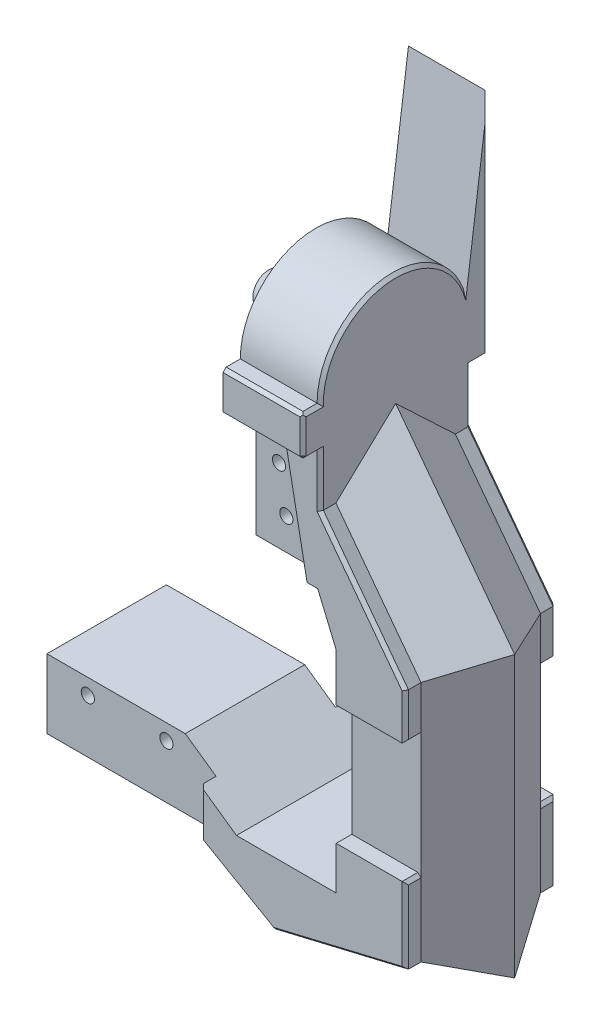
SolidWorks part; units mm, degrees
ref_plane "前视基准面" through (0, 0, 0) normal (0, 0, 1) x (1, 0, 0)
ref_plane "上视基准面" through (0, 0, 0) normal (0, 1, 0) x (1, 0, 0)
ref_plane "右视基准面" through (0, 0, 0) normal (1, 0, 0) x (0, 0, -1)
other "Configuration Table"
sketch "草图1" plane through (0, 0, 0) normal (0, 0, 1) x (1, 0, 0)
  line L0 (0, 0) -> (53.8, 0)
  line L1 (53.8, 0) -> (77, -13.3945)
  line L2 (77, -13.3945) -> (119, -3.4144)
  line L3 (119, -3.4144) -> (119, 73.5856)
  line L4 (119, 73.5856) -> (91.9365, 109.5)
  line L5 (91.9365, 109.5) -> (91.9365, 158)
  line L6 (91.9365, 158) -> (66.5044, 158)
  line L7 (66.5044, 158) -> (66.5044, 88)
  line L8 (66.5044, 88) -> (91.1544, 88)
  line L9 (91.1544, 88) -> (97, 74.0856)
  line L12 (65.3, 7.0856) -> (44, 22)
  line L13 (44, 22) -> (0, 22)
  line L14 (0, 22) -> (0, 0)
  line L15 (65.3, 7.0856) -> (97, 7.0856)
  line L16 (97, 7.0856) -> (97, 74.0856)
  circle A0 centre (73.8244, 111.53) radius 2.1
  circle A1 centre (76.1544, 98.03) radius 2.1
  circle A2 centre (13, 17) radius 2.1
  circle A3 centre (38, 17) radius 2.1
  dimension "D21" = 4.2
  dimension "D24" = 4.2
  dimension "D29" = 4.2
  dimension "D30" = 4.2
  dimension "D1" = 44
  dimension "D2" = 53
  dimension "D3" = 22
  dimension "D4" = 145
  dimension "D5" = 150
  dimension "D6" = 31.7
  dimension "D7" = 22
  dimension "D8" = 23.2
  dimension "D9" = 42
  dimension "D10" = 10.5
  dimension "D11" = 24.65
  dimension "D12" = 66
  dimension "D13" = 67.212
  dimension "D14" = 77
  dimension "D15" = 67
  dimension "D16" = 70
  dimension "D17" = 48.5
  dimension "D18" = 143
  dimension "D19" = 7.32
  dimension "D20" = 23.53
  dimension "D22" = 9.65
  dimension "D23" = 10.03
  dimension "D25" = 13
  dimension "D26" = 38
  dimension "D27" = 17
  dimension "D28" = 17
extrude "凸台-拉伸1" add sketch "草图1" along normal blind 38
sketch "草图2" plane through (91.9365, 0, 0) normal (1, 0, 0) x (0, 0, -1)
  line L0 (-38, 109.5) -> (-38, 158) construction
  line L1 (-38, 158) -> (0, 158) construction
  line L2 (0, 109.5) -> (0, 158) construction
  line L3 (-19, 109.5) -> (-19, 164.3174) construction
  line L5 (-38, 139) -> (-38, 158)
  line L6 (-38, 158) -> (0, 158)
  line L7 (0, 158) -> (0, 139)
  arc A0 (-38, 139) -> (0, 139) centre (-19, 139) cw
  circle A1 centre (-19, 139) radius 3
  line M6 (0, 109.5) -> (0, 158)
  line M7 (0, 158) -> (-38, 158)
  line M8 (-38, 158) -> (-38, 109.5)
  dimension "D1" = 6
extrude "切除-拉伸1" cut sketch "草图2" against normal through all contours A0 L6 M8 | A0 M7 M6 region at (91.9365, 153.756, 4.244) region at (91.9365, 153.756, 33.756)
sketch "草图3" plane through (66.5044, 0, 0) normal (-1, 0, 0) x (0, 0, 1)
  line L3 (0, 139) -> (0, 88)
  line L4 (0, 88) -> (38, 88)
  line L5 (38, 88) -> (38, 139)
  line L6 (0, 139) -> (0, 88)
  line L7 (0, 88) -> (38, 88)
  line L8 (38, 88) -> (38, 139)
  circle A0 centre (19, 139) radius 3
  arc A1 (38, 139) -> (0, 139) centre (19, 139) ccw
  arc A2 (38, 139) -> (0, 139) centre (19, 139) ccw
  dimension "D2" = 6
  dimension "D1" = 0
extrude "切除-拉伸3" cut sketch "草图3" against normal blind 1 contours A0
ref_plane "基准面1" through (77, 0, 0) normal (-1, 0, 0) x (0, 0, 1)
sketch "草图4" plane through (77, 0, 0) normal (-1, 0, 0) x (0, 0, 1)
  line L0 (38, -13.3945) -> (0, -13.3945) construction
  line L1 (38, -13.3945) -> (0, -13.3945)
  line L2 (0, -13.3945) -> (19, -24.4851)
  line L3 (19, -24.4851) -> (38, -13.3945)
  dimension "D1" = 22
ref_plane "基准面2" through (0, 109.5, 0) normal (0, -1, 0) x (-1, 0, 0)
sketch "草图9" plane through (0, 109.5, 0) normal (0, -1, 0) x (-1, 0, 0)
  line L0 (-91.9365, -38) -> (-91.9365, 0) construction
  line L1 (-91.9365, -38) -> (-91.9365, 0)
sketch "草图10" plane through (0, 109.5, 0) normal (0, -1, 0) x (-1, 0, 0)
  line L0 (-91.9365, 0) -> (-103.0271, -19)
  line L1 (-103.0271, -19) -> (-91.9365, -38)
  line L2 (-91.9365, 0) -> (-91.9365, -38)
  dimension "D1" = 22
ref_plane "基准面3" through (0, 0, 19) normal (0, 0, 1) x (1, 0, 0)
sketch "草图13" plane through (0, 0, 19) normal (0, 0, 1) x (1, 0, 0)
  line L3 (77, -13.3945) -> (119, -3.4144) construction
  line L10 (91.9365, 127.4291) -> (129.79, 77.1959)
  line L11 (129.79, 77.1959) -> (129.79, -11.941)
  line L12 (129.79, -11.941) -> (77, -24.4851)
  line L13 (119, 73.5856) -> (91.9365, 109.5) construction
  line L14 (91.9365, 109.5) -> (91.9365, 139) construction
  line L15 (119, 73.5856) -> (91.9365, 109.5)
  line L16 (91.9365, 109.5) -> (91.9365, 139)
  line L17 (77, -13.3945) -> (77, -24.4851) construction
  line L18 (119, -3.4144) -> (119, 73.5856) construction
  dimension "D1" = 10.79
  dimension "D2" = 10.79
  dimension "D3" = 10.7901
sweep "扫描3" add profiles "草图4" path "草图13"
sketch "草图14" plane through (0, 0, 38) normal (0, 0, 1) x (1, 0, 0)
  line L0 (66.5044, 126.1486) -> (80.4341, 126.1486)
  line L1 (80.4341, 126.1486) -> (87.7424, 88)
  line L2 (97, 58.8709) -> (118.9999, 58.8709)
  line L3 (97, 20.7689) -> (118.9999, 20.7689)
  line L4 (53.8, 0) -> (53.8, 15.138)
  line L15 (91.9365, 109.4998) -> (91.9365, 139)
  line L16 (91.9365, 139) -> (66.5044, 139)
  line L17 (66.5044, 139) -> (66.5044, 88)
  line L18 (66.5044, 88) -> (91.1544, 88)
  line L19 (91.1544, 88) -> (97, 74.0856)
  line L20 (97, 74.0856) -> (97, 7.0856)
  line L21 (97, 7.0856) -> (65.3, 7.0856)
  line L22 (65.3, 7.0856) -> (44, 22)
  line L23 (44, 22) -> (0, 22)
  line L24 (0, 22) -> (0, 0)
  line L25 (0, 0) -> (53.8, 0)
  line L26 (53.8, 0) -> (77, -13.3945)
  line L27 (77, -13.3945) -> (118.9999, -3.4144)
  line L28 (118.9999, -3.4144) -> (118.9999, 73.5855)
  line L29 (118.9999, 73.5855) -> (91.9365, 109.4998)
  line L30 (91.9365, 109.4998) -> (91.9365, 139)
  line L31 (91.9365, 139) -> (66.5044, 139)
  line L32 (66.5044, 139) -> (66.5044, 88)
  line L33 (66.5044, 88) -> (91.1544, 88)
  line L34 (91.1544, 88) -> (97, 74.0856)
  line L35 (97, 74.0856) -> (97, 7.0856)
  line L36 (97, 7.0856) -> (65.3, 7.0856)
  line L37 (65.3, 7.0856) -> (44, 22)
  line L38 (44, 22) -> (0, 22)
  line L39 (0, 22) -> (0, 0)
  line L40 (0, 0) -> (53.8, 0)
  line L41 (53.8, 0) -> (77, -13.3945)
  line L42 (77, -13.3945) -> (118.9999, -3.4144)
  line L43 (118.9999, -3.4144) -> (118.9999, 73.5855)
  line L44 (118.9999, 73.5855) -> (91.9365, 109.4998)
  line M16 (91.9365, 109.4998) -> (91.9365, 139)
  line M17 (91.9365, 139) -> (66.5044, 139)
  line M18 (66.5044, 139) -> (66.5044, 88)
  line M19 (66.5044, 88) -> (91.1544, 88)
  line M20 (91.1544, 88) -> (97, 74.0856)
  line M21 (97, 74.0856) -> (97, 7.0856)
  line M22 (97, 7.0856) -> (65.3, 7.0856)
  line M27 (53.8, 0) -> (77, -13.3945)
  line M28 (77, -13.3945) -> (118.9999, -3.4144)
  line M29 (118.9999, -3.4144) -> (118.9999, 73.5855)
  line M30 (118.9999, 73.5855) -> (91.9365, 109.4998)
  dimension "D1" = 0
extrude "凸台-拉伸2" add sketch "草图14" along normal blind 5 contours L3 M22 M27 M28 M29 M21 | L2 L0 L1 M21 M29 M30 M16 M17 M18 M19 M20 region at (94.8648, 97.4527, 38) region at (90.2976, 2.9827, 38)
sketch "草图15" plane through (0, 0, 0) normal (0, 0, -1) x (-1, 0, 0)
  line L0 (-53.8, 0) -> (-53.8, 15.138) construction
  line L1 (-97, 20.7689) -> (-118.9999, 20.7689) construction
  line L2 (-97, 58.8709) -> (-118.9999, 58.8709) construction
  line L3 (-80.4341, 126.1486) -> (-87.7424, 88) construction
  line L4 (-66.5044, 126.1486) -> (-80.4341, 126.1486) construction
  line L5 (-53.8, 0) -> (-53.8, 15.138)
  line L6 (-97, 20.7689) -> (-118.9999, 20.7689)
  line L7 (-97, 58.8709) -> (-118.9999, 58.8709)
  line L8 (-80.4341, 126.1486) -> (-87.7424, 88)
  line L9 (-66.5044, 126.1486) -> (-80.4341, 126.1486)
  line L15 (-91.9365, 139) -> (-91.9365, 109.4998)
  line L16 (-91.9365, 109.4998) -> (-118.9999, 73.5855)
  line L17 (-118.9999, 73.5855) -> (-118.9999, -3.4144)
  line L18 (-118.9999, -3.4144) -> (-77, -13.3945)
  line L19 (-77, -13.3945) -> (-53.8, 0)
  line L20 (-53.8, 0) -> (0, 0)
  line L21 (0, 0) -> (0, 22)
  line L22 (0, 22) -> (-44, 22)
  line L23 (-44, 22) -> (-65.3, 7.0856)
  line L24 (-65.3, 7.0856) -> (-97, 7.0856)
  line L25 (-97, 7.0856) -> (-97, 74.0856)
  line L26 (-97, 74.0856) -> (-91.1544, 88)
  line L27 (-91.1544, 88) -> (-66.5044, 88)
  line L28 (-66.5044, 88) -> (-66.5044, 139)
  line L29 (-66.5044, 139) -> (-91.9365, 139)
  line L30 (-91.9365, 139) -> (-91.9365, 109.4998)
  line L31 (-91.9365, 109.4998) -> (-118.9999, 73.5855)
  line L32 (-118.9999, 73.5855) -> (-118.9999, -3.4144)
  line L33 (-118.9999, -3.4144) -> (-77, -13.3945)
  line L34 (-77, -13.3945) -> (-53.8, 0)
  line L35 (-53.8, 0) -> (0, 0)
  line L36 (0, 0) -> (0, 22)
  line L37 (0, 22) -> (-44, 22)
  line L38 (-44, 22) -> (-65.3, 7.0856)
  line L39 (-65.3, 7.0856) -> (-97, 7.0856)
  line L40 (-97, 7.0856) -> (-97, 74.0856)
  line L41 (-97, 74.0856) -> (-91.1544, 88)
  line L42 (-91.1544, 88) -> (-66.5044, 88)
  line L43 (-66.5044, 88) -> (-66.5044, 139)
  line L44 (-66.5044, 139) -> (-91.9365, 139)
  line M16 (-91.9365, 139) -> (-91.9365, 109.4998)
  line M17 (-91.9365, 109.4998) -> (-118.9999, 73.5855)
  line M18 (-118.9999, 73.5855) -> (-118.9999, -3.4144)
  line M19 (-118.9999, -3.4144) -> (-77, -13.3945)
  line M20 (-77, -13.3945) -> (-53.8, 0)
  line M24 (-44, 22) -> (-65.3, 7.0856)
  line M25 (-65.3, 7.0856) -> (-97, 7.0856)
  line M26 (-97, 7.0856) -> (-97, 74.0856)
  line M27 (-97, 74.0856) -> (-91.1544, 88)
  line M28 (-91.1544, 88) -> (-66.5044, 88)
  line M29 (-66.5044, 88) -> (-66.5044, 139)
  line M30 (-66.5044, 139) -> (-91.9365, 139)
  dimension "D1" = 0
extrude "凸台-拉伸3" add sketch "草图15" along normal blind 5 contours L9 L7 L8 M29 M30 M16 M17 M18 M26 M27 M28 | L6 L5 M26 M18 M19 M20 M24 M25 region at (90.2976, 2.9827, 0) region at (94.8648, 97.4527, 0)
sketch "草图16" plane through (91.9365, 0, 0) normal (1, 0, 0) x (0, 0, -1)
  line L0 (-43, 109.4998) -> (-43, 139) construction
  arc A0 (-43, 139) -> (5, 139) centre (-19, 139) cw
extrude "拉伸-薄壁2" add sketch "草图16" along direction (1, 0, 0) on the side against the normal up to surface (25.4322 mm away) thin up to face at (66.5044, 136, 19) thin type one direction wall 10
sketch "草图17" plane through (91.9365, 0, 0) normal (1, 0, 0) x (0, 0, -1)
  line L0 (5, 128.4582) -> (10.5, 128.4582)
  line L3 (10.5, 128.4582) -> (10.5, 198.4582)
  line L4 (10.5, 198.4582) -> (3.6023, 147.0707)
  line L6 (-43, 139) -> (-43, 109.4998)
  line L7 (-43, 109.4998) -> (-38, 109.4998)
  line L8 (-38, 109.4998) -> (-19, 127.4291)
  line L9 (-19, 127.4291) -> (0, 109.4998)
  line L10 (0, 109.4998) -> (5, 109.4998)
  line L11 (5, 109.4998) -> (5, 139)
  line L12 (-43, 139) -> (-43, 109.4998)
  line L13 (-43, 109.4998) -> (-38, 109.4998)
  line L14 (-38, 109.4998) -> (-19, 127.4291)
  line L15 (-19, 127.4291) -> (0, 109.4998)
  line L16 (0, 109.4998) -> (5, 109.4998)
  line L17 (5, 109.4998) -> (5, 139)
  arc A1 (5, 139) -> (-43, 139) centre (-19, 139) ccw
  arc A2 (5, 139) -> (-43, 139) centre (-19, 139) ccw
  point P7 (3.6023, 147.0707)
  arc M10 (5, 139) -> (-43, 139) centre (-19, 139) ccw
  line M16 (5, 109.4998) -> (5, 139)
  dimension "D2" = 5.5
  dimension "D3" = 70
  dimension "D1" = 0
extrude "凸台-拉伸7" add sketch "草图17" against normal up to surface (25.4322 mm away) contours L3 L4 L0 M10 M16 region at (91.9365, 154.397, -7.9904) up to face at (66.5044, 122.8243, 19)
sketch "草图18" plane through (0, 128.4582, 0) normal (0, -1, 0) x (1, 0, 0)
  line L4 (66.5044, -5) -> (66.5044, -10.5)
  line L5 (66.5044, -10.5) -> (91.9365, -10.5)
  line L6 (91.9365, -10.5) -> (91.9365, -5)
  line L7 (91.9365, -5) -> (66.5044, -5)
  line L8 (66.5044, -5) -> (66.5044, -10.5)
  line L9 (66.5044, -10.5) -> (91.9365, -10.5)
  line L10 (91.9365, -10.5) -> (91.9365, -5)
  line L11 (91.9365, -5) -> (66.5044, -5)
  dimension "D1" = 0
extrude "凸台-拉伸8" add sketch "草图18" along normal up to surface (2.3096 mm away) up to face at (73.4692, 126.1486, -2.5)
sketch "草图19" plane through (0, 0, 43) normal (0, 0, 1) x (1, 0, 0)
  line L0 (80.4341, 126.1486) -> (91.9365, 126.1486)
  line L11 (97, 74.0856) -> (97, 58.8709)
  line L12 (97, 58.8709) -> (118.9999, 58.8709)
  line L13 (118.9999, 58.8709) -> (118.9999, 73.5855)
  line L14 (118.9999, 73.5855) -> (91.9365, 109.4998)
  line L15 (91.9365, 109.4998) -> (91.9365, 139)
  line L16 (91.9365, 139) -> (66.5044, 139)
  line L17 (66.5044, 139) -> (66.5044, 126.1486)
  line L18 (66.5044, 126.1486) -> (80.4341, 126.1486)
  line L19 (80.4341, 126.1486) -> (87.7424, 88)
  line L20 (87.7424, 88) -> (91.1544, 88)
  line L21 (91.1544, 88) -> (97, 74.0856)
  line L26 (91.9365, 126.1486) -> (91.9365, 139)
  line L27 (91.9365, 139) -> (66.5044, 139)
  line L28 (66.5044, 139) -> (66.5044, 126.1486)
  line L29 (66.5044, 126.1486) -> (80.4341, 126.1486)
  line L31 (87.7424, 88) -> (91.1544, 88)
  line M16 (91.9365, 109.4998) -> (91.9365, 139)
  line M17 (91.9365, 139) -> (66.5044, 139)
  line M18 (66.5044, 139) -> (66.5044, 126.1486)
  line M19 (66.5044, 126.1486) -> (80.4341, 126.1486)
  dimension "D1" = 0
extrude "凸台-拉伸10" add sketch "草图19" along normal blind 5.5 contours L0 M19 M16 M17 M18 region at (79.2205, 132.5743, 43)
sketch "草图20" plane through (66.5044, 0, 0) normal (-1, 0, 0) x (0, 0, 1)
  line L9 (-10.5, 198.4582) -> (-10.5, 126.1486)
  line L10 (-10.5, 126.1486) -> (0, 126.1486)
  line L11 (0, 126.1486) -> (0, 88)
  line L12 (0, 88) -> (38, 88)
  line L13 (38, 88) -> (38, 126.1486)
  line L14 (38, 126.1486) -> (48.5, 126.1486)
  line L15 (48.5, 126.1486) -> (48.5, 139)
  line L16 (48.5, 139) -> (43, 139)
  line L17 (-3.6023, 147.0707) -> (-10.5, 198.4582)
  line L18 (-10.5, 198.4582) -> (-10.5, 126.1486)
  line L19 (-10.5, 126.1486) -> (0, 126.1486)
  line L20 (0, 126.1486) -> (0, 88)
  line L21 (0, 88) -> (38, 88)
  line L22 (38, 88) -> (38, 126.1486)
  line L23 (38, 126.1486) -> (48.5, 126.1486)
  line L24 (48.5, 126.1486) -> (48.5, 139)
  line L25 (48.5, 139) -> (43, 139)
  line L26 (-3.6023, 147.0707) -> (-10.5, 198.4582)
  circle A0 centre (19, 139) radius 3 construction
  arc A1 (43, 139) -> (-3.6023, 147.0707) centre (19, 139) ccw
  arc A2 (43, 139) -> (-3.6023, 147.0707) centre (19, 139) ccw
  circle A3 centre (19, 139) radius 3
  circle A4 centre (19, 139) radius 13
  dimension "D2" = 26
  dimension "D1" = 0
ref_plane "基准面4" through (51.5044, 0, 0) normal (-1, 0, 0) x (0, 0, 1)
sketch "草图21" plane through (51.5044, 0, 0) normal (-1, 0, 0) x (0, 0, 1)
  circle A0 centre (19, 139) radius 13 construction
  circle A1 centre (19, 139) radius 3 construction
  circle A2 centre (19, 139) radius 13
  circle A3 centre (19, 139) radius 3
  circle A4 centre (19, 139) radius 5
  dimension "D1" = 10
loft "放样1" add section "草图21" section "草图20" connector at (51.5044, 140.2647, 23.8374) connector at (66.5044, 141.5722, 31.743)
sketch "草图23" plane through (51.5044, 0, 0) normal (-1, 0, 0) x (0, 0, 1)
  circle A0 centre (19, 139) radius 3
  circle A1 centre (19, 139) radius 5
  circle A2 centre (19, 139) radius 5
  dimension "D2" = 6
  dimension "D1" = 0
extrude "切除-拉伸4" cut sketch "草图23" against normal up to next contours A0
chamfer "倒角1" distance 1 angle 45 1 edges at (79.2205, 139, 48.5)
chamfer "倒角3" distance 1 angle 45 25 edges at (118.9999, 58.8709, -2.5) (118.9999, 66.2282, -5) (105.4682, 91.5427, -5) (91.9365, 117.8242, -5) (91.9365, 126.1486, -7.75) (91.9365, 162.3034, -10.5) (91.9365, 162.648, 23.0954) (91.9365, 139, 45.25) (79.2205, 126.1486, 48.5) (118.9999, 58.8709, 40.5) (91.9365, 132.0743, 48.5) (91.9365, 126.1486, 45.75) (91.9365, 117.8242, 43) (105.4682, 91.5427, 43) (118.9999, 66.2282, 43) (118.9999, 20.7689, -2.5) (118.9999, 8.6772, -5) (98, -8.4045, -5) (65.4, -6.6973, -5) (53.8, 7.569, -5) (118.9999, 20.7689, 40.5) (118.9999, 8.6772, 43) (98, -8.4045, 43) (65.4, -6.6973, 43) (53.8, 7.569, 43)
